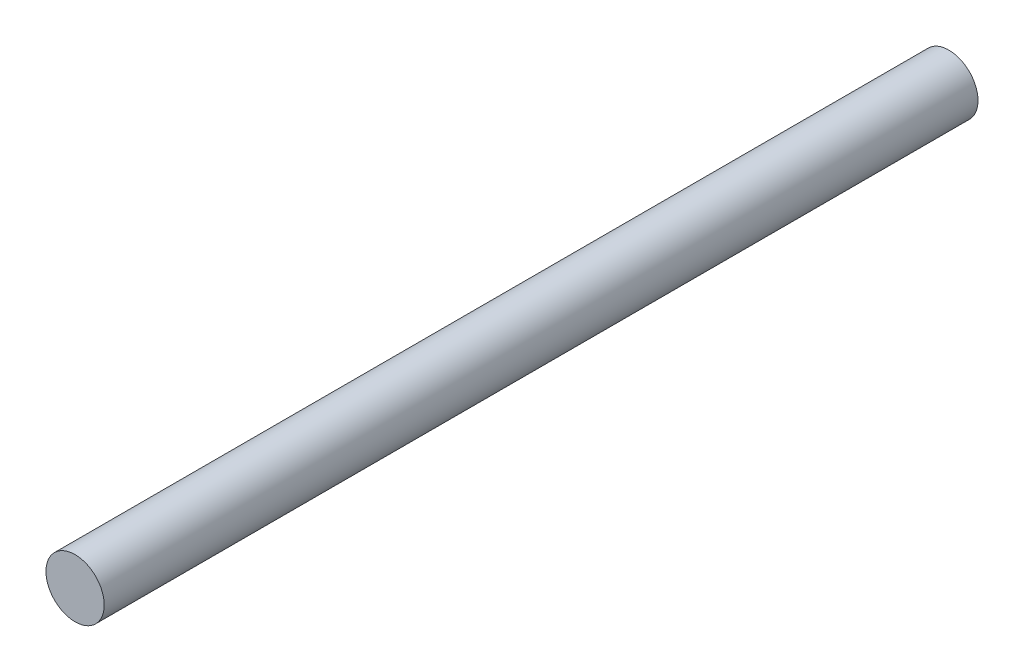
SolidWorks part; units mm, degrees
ref_plane "Front Plane" through (0, 0, 0) normal (0, 0, 1) x (1, 0, 0)
ref_plane "Top Plane" through (0, 0, 0) normal (0, 1, 0) x (1, 0, 0)
ref_plane "Right Plane" through (0, 0, 0) normal (1, 0, 0) x (0, 0, -1)
sketch "Sketch1" plane through (0, 0, 0) normal (0, 0, 1) x (1, 0, 0)
  circle A0 centre (0, 0) radius 4
extrude "Rod" add sketch "Sketch1" along normal blind 120
